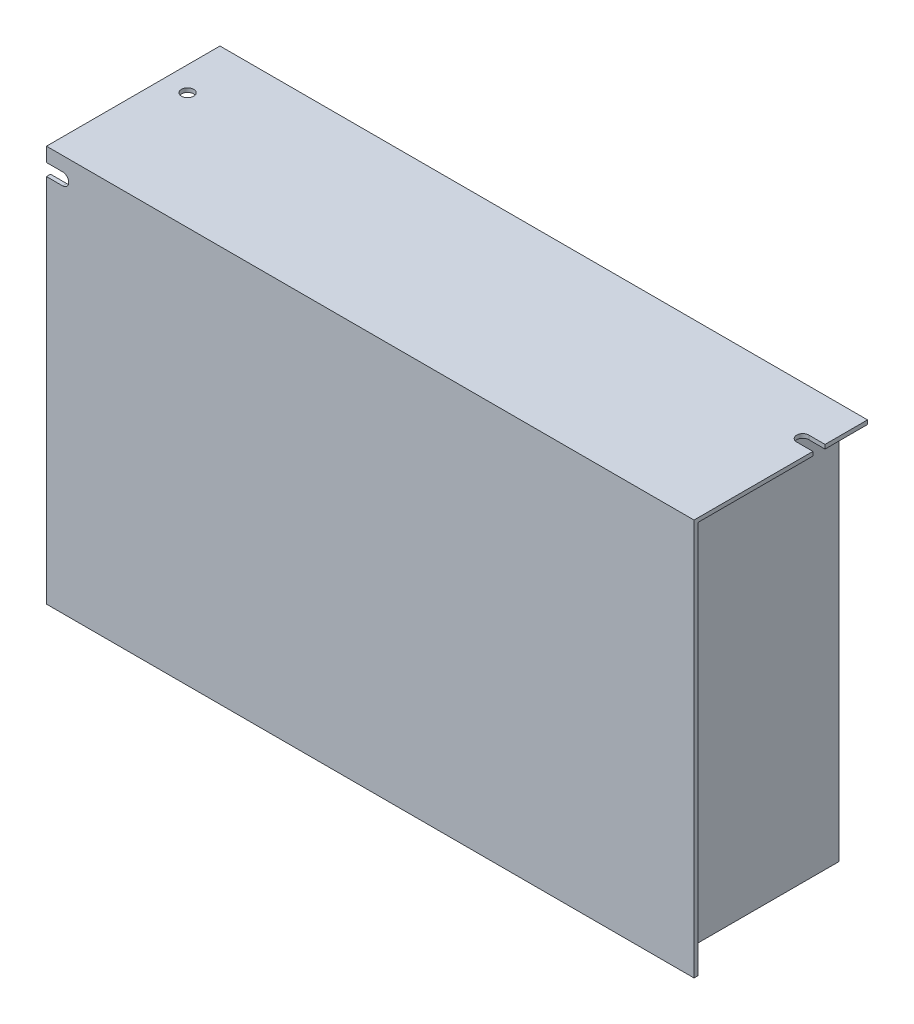
SolidWorks part; units mm, degrees
ref_plane "前视基准面" through (0, 0, 0) normal (0, 0, 1) x (1, 0, 0)
ref_plane "上视基准面" through (0, 0, 0) normal (0, 1, 0) x (1, 0, 0)
ref_plane "右视基准面" through (0, 0, 0) normal (1, 0, 0) x (0, 0, -1)
other "Configuration Table"
sketch "草图1" plane through (0, 0, 0) normal (0, 1, 0) x (1, 0, 0)
  line L1 (0, 42.8682) -> (140, 42.8682)
  line L2 (0, 42.8682) -> (0, 0)
  line L3 (0, 0) -> (140, 0)
  line L4 (140, 42.8682) -> (140, 0)
  dimension "D1" = 140
extrude "凸台-拉伸1" add sketch "草图1" against normal blind 98
sketch "草图3" plane through (0, 0, 0) normal (-1, 0, 0) x (0, 0, 1)
  line L0 (0, -98) -> (-1, -98)
  line L1 (-42.8682, -98) -> (0, -98) construction
  line L2 (-1, -98) -> (-1, -1)
  line L3 (-1, -1) -> (-42.8682, -1)
  line L4 (-42.8682, -98) -> (-42.8682, 0) construction
  line L5 (-42.8682, -1) -> (-42.8682, 0)
  line L6 (-42.8682, 0) -> (0, 0)
  line L7 (0, 0) -> (0, -98)
  dimension "D1" = 1
  dimension "D2" = 1
extrude "凸台-拉伸2" add sketch "草图3" along normal blind 13
sketch "草图4" plane through (140, 0, 0) normal (1, 0, 0) x (0, 0, -1)
  line L0 (42.8682, 0) -> (42.8682, -1)
  line L1 (42.8682, -98) -> (42.8682, 0) construction
  line L2 (42.8682, -1) -> (1, -1)
  line L3 (1, -1) -> (1, -98)
  line L4 (0, -98) -> (42.8682, -98) construction
  line L5 (1, -98) -> (0, -98)
  line L6 (0, -98) -> (0, 0)
  line L7 (0, 0) -> (42.8682, 0)
  dimension "D1" = 1
  dimension "D2" = 1
extrude "凸台-拉伸3" add sketch "草图4" along normal blind 7
sketch "草图5" plane through (0, 0, -1) normal (0, 0, -1) x (-1, 0, 0)
  line L0 (21, -5) -> (9, -5) construction
  line L1 (21, -6.5) -> (9, -6.5)
  line L2 (21, -3.5) -> (9, -3.5)
  line L3 (13, 0) -> (-147, 0) construction
  line L4 (13, -1) -> (13, -98) construction
  arc A0 (21, -6.5) -> (21, -3.5) centre (21, -5) ccw
  arc A1 (9, -3.5) -> (9, -6.5) centre (9, -5) ccw
  point P2 (15, -5)
  point P9 (9.4578, -5)
  dimension "D1" = 1.5
  dimension "D2" = 5
  dimension "D3" = 4
  dimension "D4" = 12
extrude "切除-拉伸1" cut sketch "草图5" against normal blind 7
sketch "草图6" plane through (0, -1, 0) normal (0, -1, 0) x (1, 0, 0)
  line L0 (-13, -42.8682) -> (-13, -1) construction
  line L1 (-13, -42.8682) -> (0, -42.8682) construction
  circle A0 centre (-7, -28.8682) radius 1.5
  point P2 (-7.2335, -34.7698)
  dimension "D1" = 3
  dimension "D2" = 6
  dimension "D3" = 14
extrude "切除-拉伸2" cut sketch "草图6" against normal blind 7
sketch "草图7" plane through (0, -1, 0) normal (0, -1, 0) x (1, 0, 0)
  line L0 (143, -30.8682) -> (151, -30.8682) construction
  line L1 (143, -29.3682) -> (151, -29.3682)
  line L2 (143, -32.3682) -> (151, -32.3682)
  line L3 (147, -42.8682) -> (140, -42.8682) construction
  line L4 (147, -1) -> (147, -42.8682) construction
  arc A0 (143, -29.3682) -> (143, -32.3682) centre (143, -30.8682) ccw
  arc A1 (151, -32.3682) -> (151, -29.3682) centre (151, -30.8682) ccw
  point P2 (147, -30.8682)
  dimension "D1" = 1.5
  dimension "D2" = 12
  dimension "D3" = 4
  dimension "D4" = 8
extrude "切除-拉伸3" cut sketch "草图7" against normal blind 7
shell "抽壳2" thickness 1 removed face at (0, -49.5, -21.9341)
sketch "草图8" plane through (0, 0, -1) normal (0, 0, -1) x (-1, 0, 0)
  line L0 (13, -6.5) -> (13, -98) construction
  line L1 (0, -18) -> (13, -18)
  line L2 (0, -18) -> (0, -88)
  line L3 (0, -88) -> (13, -88)
  line L4 (13, -18) -> (13, -88)
  line L5 (0, -98) -> (0, -1) construction
  line L6 (13, -98) -> (0, -98) construction
  line L8 (13, -1) -> (-139, -1) construction
  point P6 (0, -15.1137)
  dimension "D1" = 10
  dimension "D2" = 17
extrude "凸台-拉伸4" add sketch "草图8" along normal blind 20
sketch "草图9" plane through (0, 0, 0) normal (-1, 0, 0) x (0, 0, 1)
  line L0 (-42.8682, -1) -> (-1, -1) construction
  line L1 (-42.8682, -98) -> (-30.8682, -98)
  line L2 (-42.8682, -98) -> (-42.8682, -1)
  line L3 (-42.8682, -1) -> (-30.8682, -1)
  line L4 (-30.8682, -98) -> (-30.8682, -1)
  dimension "D1" = 12
extrude "凸台-拉伸5" add sketch "草图9" against normal blind 1
sketch "草图10" plane through (0, 0, -42.8682) normal (0, 0, -1) x (-1, 0, 0)
  circle A0 centre (-135.5089, -6.634) radius 2
  circle A1 centre (-129.5089, -12.634) radius 2
  circle A2 centre (-119.5089, -12.634) radius 2
  circle A3 centre (-125.5089, -6.634) radius 2
  circle A4 centre (-109.5089, -12.634) radius 2
  circle A5 centre (-115.5089, -6.634) radius 2
  circle A6 centre (-99.5089, -12.634) radius 2
  circle A7 centre (-105.5089, -6.634) radius 2
  circle A8 centre (-89.5089, -12.634) radius 2
  circle A9 centre (-95.5089, -6.634) radius 2
  circle A10 centre (-79.5089, -12.634) radius 2
  circle A11 centre (-85.5089, -6.634) radius 2
  circle A12 centre (-69.5089, -12.634) radius 2
  circle A13 centre (-75.5089, -6.634) radius 2
  circle A14 centre (-59.5089, -12.634) radius 2
  circle A15 centre (-65.5089, -6.634) radius 2
  circle A16 centre (-49.5089, -12.634) radius 2
  circle A17 centre (-55.5089, -6.634) radius 2
  circle A18 centre (-39.5089, -12.634) radius 2
  circle A19 centre (-45.5089, -6.634) radius 2
  circle A20 centre (-29.5089, -12.634) radius 2
  circle A21 centre (-35.5089, -6.634) radius 2
  circle A22 centre (-19.5089, -12.634) radius 2
  circle A23 centre (-25.5089, -6.634) radius 2
  circle A24 centre (-9.5089, -12.634) radius 2
  circle A25 centre (-15.5089, -6.634) radius 2
  circle A26 centre (-119.5089, -22.634) radius 2
  circle A27 centre (-125.5089, -16.634) radius 2
  circle A28 centre (-109.5089, -22.634) radius 2
  circle A29 centre (-115.5089, -16.634) radius 2
  circle A30 centre (-99.5089, -22.634) radius 2
  circle A31 centre (-105.5089, -16.634) radius 2
  circle A32 centre (-89.5089, -22.634) radius 2
  circle A33 centre (-95.5089, -16.634) radius 2
  circle A34 centre (-79.5089, -22.634) radius 2
  circle A35 centre (-85.5089, -16.634) radius 2
  circle A36 centre (-69.5089, -22.634) radius 2
  circle A37 centre (-75.5089, -16.634) radius 2
  circle A38 centre (-59.5089, -22.634) radius 2
  circle A39 centre (-65.5089, -16.634) radius 2
  circle A40 centre (-49.5089, -22.634) radius 2
  circle A41 centre (-55.5089, -16.634) radius 2
  circle A42 centre (-39.5089, -22.634) radius 2
  circle A43 centre (-45.5089, -16.634) radius 2
  circle A44 centre (-29.5089, -22.634) radius 2
  circle A45 centre (-35.5089, -16.634) radius 2
  circle A46 centre (-19.5089, -22.634) radius 2
  circle A47 centre (-25.5089, -16.634) radius 2
  circle A48 centre (-9.5089, -22.634) radius 2
  circle A49 centre (-15.5089, -16.634) radius 2
  circle A50 centre (-119.5089, -32.634) radius 2
  circle A51 centre (-125.5089, -26.634) radius 2
  circle A52 centre (-109.5089, -32.634) radius 2
  circle A53 centre (-115.5089, -26.634) radius 2
  circle A54 centre (-99.5089, -32.634) radius 2
  circle A55 centre (-105.5089, -26.634) radius 2
  circle A56 centre (-89.5089, -32.634) radius 2
  circle A57 centre (-95.5089, -26.634) radius 2
  circle A58 centre (-79.5089, -32.634) radius 2
  circle A59 centre (-85.5089, -26.634) radius 2
  circle A60 centre (-69.5089, -32.634) radius 2
  circle A61 centre (-75.5089, -26.634) radius 2
  circle A62 centre (-59.5089, -32.634) radius 2
  circle A63 centre (-65.5089, -26.634) radius 2
  circle A64 centre (-49.5089, -32.634) radius 2
  circle A65 centre (-55.5089, -26.634) radius 2
  circle A66 centre (-39.5089, -32.634) radius 2
  circle A67 centre (-45.5089, -26.634) radius 2
  circle A68 centre (-29.5089, -32.634) radius 2
  circle A69 centre (-35.5089, -26.634) radius 2
  circle A70 centre (-19.5089, -32.634) radius 2
  circle A71 centre (-25.5089, -26.634) radius 2
  circle A72 centre (-9.5089, -32.634) radius 2
  circle A73 centre (-15.5089, -26.634) radius 2
  circle A74 centre (-119.5089, -42.634) radius 2
  circle A75 centre (-125.5089, -36.634) radius 2
  circle A76 centre (-109.5089, -42.634) radius 2
  circle A77 centre (-115.5089, -36.634) radius 2
  circle A78 centre (-99.5089, -42.634) radius 2
  circle A79 centre (-105.5089, -36.634) radius 2
  circle A80 centre (-89.5089, -42.634) radius 2
  circle A81 centre (-95.5089, -36.634) radius 2
  circle A82 centre (-79.5089, -42.634) radius 2
  circle A83 centre (-85.5089, -36.634) radius 2
  circle A84 centre (-69.5089, -42.634) radius 2
  circle A85 centre (-75.5089, -36.634) radius 2
  circle A86 centre (-59.5089, -42.634) radius 2
  circle A87 centre (-65.5089, -36.634) radius 2
  circle A88 centre (-49.5089, -42.634) radius 2
  circle A89 centre (-55.5089, -36.634) radius 2
  circle A90 centre (-39.5089, -42.634) radius 2
  circle A91 centre (-45.5089, -36.634) radius 2
  circle A92 centre (-29.5089, -42.634) radius 2
  circle A93 centre (-35.5089, -36.634) radius 2
  circle A94 centre (-19.5089, -42.634) radius 2
  circle A95 centre (-25.5089, -36.634) radius 2
  circle A96 centre (-9.5089, -42.634) radius 2
  circle A97 centre (-15.5089, -36.634) radius 2
  circle A98 centre (-119.5089, -52.634) radius 2
  circle A99 centre (-125.5089, -46.634) radius 2
  circle A100 centre (-109.5089, -52.634) radius 2
  circle A101 centre (-115.5089, -46.634) radius 2
  circle A102 centre (-99.5089, -52.634) radius 2
  circle A103 centre (-105.5089, -46.634) radius 2
  circle A104 centre (-89.5089, -52.634) radius 2
  circle A105 centre (-95.5089, -46.634) radius 2
  circle A106 centre (-79.5089, -52.634) radius 2
  circle A107 centre (-85.5089, -46.634) radius 2
  circle A108 centre (-69.5089, -52.634) radius 2
  circle A109 centre (-75.5089, -46.634) radius 2
  circle A110 centre (-59.5089, -52.634) radius 2
  circle A111 centre (-65.5089, -46.634) radius 2
  circle A112 centre (-49.5089, -52.634) radius 2
  circle A113 centre (-55.5089, -46.634) radius 2
  circle A114 centre (-39.5089, -52.634) radius 2
  circle A115 centre (-45.5089, -46.634) radius 2
  circle A116 centre (-29.5089, -52.634) radius 2
  circle A117 centre (-35.5089, -46.634) radius 2
  circle A118 centre (-19.5089, -52.634) radius 2
  circle A119 centre (-25.5089, -46.634) radius 2
  circle A120 centre (-9.5089, -52.634) radius 2
  circle A121 centre (-15.5089, -46.634) radius 2
  circle A122 centre (-119.5089, -62.634) radius 2
  circle A123 centre (-125.5089, -56.634) radius 2
  circle A124 centre (-109.5089, -62.634) radius 2
  circle A125 centre (-115.5089, -56.634) radius 2
  circle A126 centre (-99.5089, -62.634) radius 2
  circle A127 centre (-105.5089, -56.634) radius 2
  circle A128 centre (-89.5089, -62.634) radius 2
  circle A129 centre (-95.5089, -56.634) radius 2
  circle A130 centre (-79.5089, -62.634) radius 2
  circle A131 centre (-85.5089, -56.634) radius 2
  circle A132 centre (-69.5089, -62.634) radius 2
  circle A133 centre (-75.5089, -56.634) radius 2
  circle A134 centre (-59.5089, -62.634) radius 2
  circle A135 centre (-65.5089, -56.634) radius 2
  circle A136 centre (-49.5089, -62.634) radius 2
  circle A137 centre (-55.5089, -56.634) radius 2
  circle A138 centre (-39.5089, -62.634) radius 2
  circle A139 centre (-45.5089, -56.634) radius 2
  circle A140 centre (-29.5089, -62.634) radius 2
  circle A141 centre (-35.5089, -56.634) radius 2
  circle A142 centre (-19.5089, -62.634) radius 2
  circle A143 centre (-25.5089, -56.634) radius 2
  circle A144 centre (-9.5089, -62.634) radius 2
  circle A145 centre (-15.5089, -56.634) radius 2
  circle A146 centre (-119.5089, -72.634) radius 2
  circle A147 centre (-125.5089, -66.634) radius 2
  circle A148 centre (-109.5089, -72.634) radius 2
  circle A149 centre (-115.5089, -66.634) radius 2
  circle A150 centre (-99.5089, -72.634) radius 2
  circle A151 centre (-105.5089, -66.634) radius 2
  circle A152 centre (-89.5089, -72.634) radius 2
  circle A153 centre (-95.5089, -66.634) radius 2
  circle A154 centre (-79.5089, -72.634) radius 2
  circle A155 centre (-85.5089, -66.634) radius 2
  circle A156 centre (-69.5089, -72.634) radius 2
  circle A157 centre (-75.5089, -66.634) radius 2
  circle A158 centre (-59.5089, -72.634) radius 2
  circle A159 centre (-65.5089, -66.634) radius 2
  circle A160 centre (-49.5089, -72.634) radius 2
  circle A161 centre (-55.5089, -66.634) radius 2
  circle A162 centre (-39.5089, -72.634) radius 2
  circle A163 centre (-45.5089, -66.634) radius 2
  circle A164 centre (-29.5089, -72.634) radius 2
  circle A165 centre (-35.5089, -66.634) radius 2
  circle A166 centre (-19.5089, -72.634) radius 2
  circle A167 centre (-25.5089, -66.634) radius 2
  circle A168 centre (-9.5089, -72.634) radius 2
  circle A169 centre (-15.5089, -66.634) radius 2
  circle A170 centre (-119.5089, -82.634) radius 2
  circle A171 centre (-125.5089, -76.634) radius 2
  circle A172 centre (-109.5089, -82.634) radius 2
  circle A173 centre (-115.5089, -76.634) radius 2
  circle A174 centre (-99.5089, -82.634) radius 2
  circle A175 centre (-105.5089, -76.634) radius 2
  circle A176 centre (-89.5089, -82.634) radius 2
  circle A177 centre (-95.5089, -76.634) radius 2
  circle A178 centre (-79.5089, -82.634) radius 2
  circle A179 centre (-85.5089, -76.634) radius 2
  circle A180 centre (-69.5089, -82.634) radius 2
  circle A181 centre (-75.5089, -76.634) radius 2
  circle A182 centre (-59.5089, -82.634) radius 2
  circle A183 centre (-65.5089, -76.634) radius 2
  circle A184 centre (-49.5089, -82.634) radius 2
  circle A185 centre (-55.5089, -76.634) radius 2
  circle A186 centre (-39.5089, -82.634) radius 2
  circle A187 centre (-45.5089, -76.634) radius 2
  circle A188 centre (-29.5089, -82.634) radius 2
  circle A189 centre (-35.5089, -76.634) radius 2
  circle A190 centre (-19.5089, -82.634) radius 2
  circle A191 centre (-25.5089, -76.634) radius 2
  circle A192 centre (-9.5089, -82.634) radius 2
  circle A193 centre (-15.5089, -76.634) radius 2
  circle A194 centre (-119.5089, -92.634) radius 2
  circle A195 centre (-125.5089, -86.634) radius 2
  circle A196 centre (-109.5089, -92.634) radius 2
  circle A197 centre (-115.5089, -86.634) radius 2
  circle A198 centre (-99.5089, -92.634) radius 2
  circle A199 centre (-105.5089, -86.634) radius 2
  circle A200 centre (-89.5089, -92.634) radius 2
  circle A201 centre (-95.5089, -86.634) radius 2
  circle A202 centre (-79.5089, -92.634) radius 2
  circle A203 centre (-85.5089, -86.634) radius 2
  circle A204 centre (-69.5089, -92.634) radius 2
  circle A205 centre (-75.5089, -86.634) radius 2
  circle A206 centre (-59.5089, -92.634) radius 2
  circle A207 centre (-65.5089, -86.634) radius 2
  circle A208 centre (-49.5089, -92.634) radius 2
  circle A209 centre (-55.5089, -86.634) radius 2
  circle A210 centre (-39.5089, -92.634) radius 2
  circle A211 centre (-45.5089, -86.634) radius 2
  circle A212 centre (-29.5089, -92.634) radius 2
  circle A213 centre (-35.5089, -86.634) radius 2
  circle A214 centre (-19.5089, -92.634) radius 2
  circle A215 centre (-25.5089, -86.634) radius 2
  circle A216 centre (-9.5089, -92.634) radius 2
  circle A217 centre (-15.5089, -86.634) radius 2
  circle A218 centre (-129.5089, -22.634) radius 2
  circle A219 centre (-135.5089, -16.634) radius 2
  circle A220 centre (-129.5089, -32.634) radius 2
  circle A221 centre (-135.5089, -26.634) radius 2
  circle A222 centre (-129.5089, -42.634) radius 2
  circle A223 centre (-135.5089, -36.634) radius 2
  circle A224 centre (-129.5089, -52.634) radius 2
  circle A225 centre (-135.5089, -46.634) radius 2
  circle A226 centre (-129.5089, -62.634) radius 2
  circle A227 centre (-135.5089, -56.634) radius 2
  circle A228 centre (-129.5089, -72.634) radius 2
  circle A229 centre (-135.5089, -66.634) radius 2
  circle A230 centre (-129.5089, -82.634) radius 2
  circle A231 centre (-135.5089, -76.634) radius 2
  circle A232 centre (-129.5089, -92.634) radius 2
  circle A233 centre (-135.5089, -86.634) radius 2
  dimension "D1" = 4
  dimension "D2" = 6
  dimension "D3" = 6
  dimension "D4" = 13
  dimension "D5" = 9
extrude "切除-拉伸4" cut sketch "草图10" against normal blind 1
